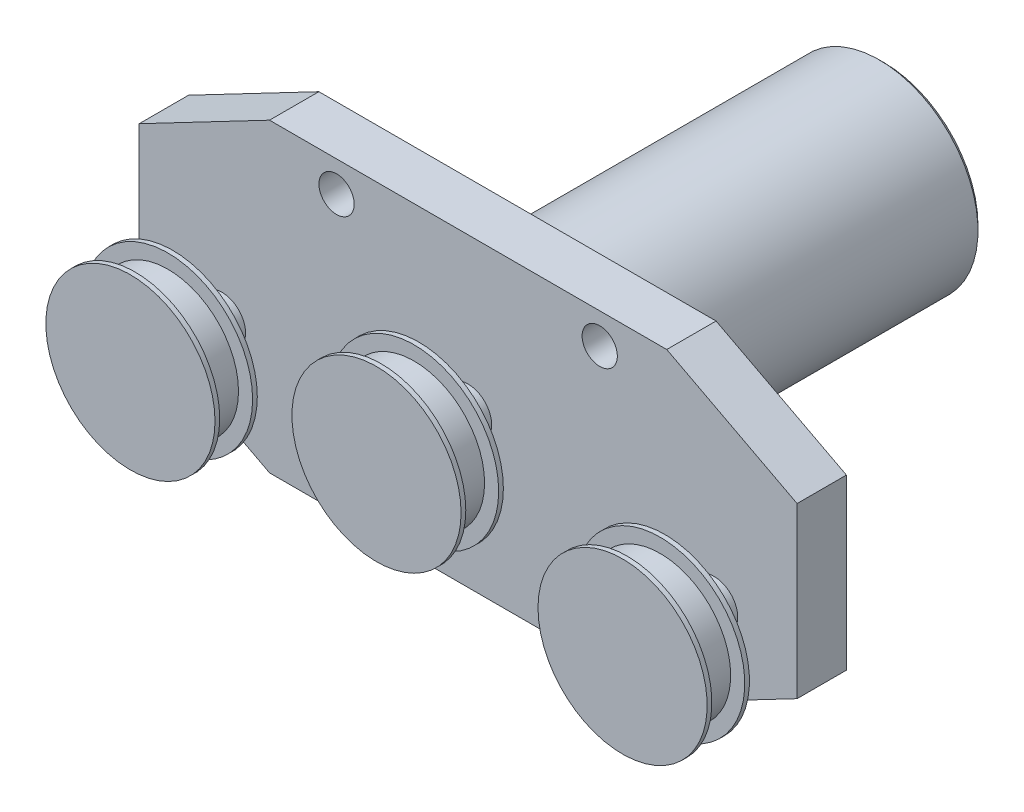
SolidWorks part; units mm, degrees
ref_plane "Front Plane" through (0, 0, 0) normal (0, 0, 1) x (1, 0, 0)
ref_plane "Top Plane" through (0, 0, 0) normal (0, 1, 0) x (1, 0, 0)
ref_plane "Right Plane" through (0, 0, 0) normal (1, 0, 0) x (0, 0, -1)
sketch "Sketch1" plane through (0, 0, 0) normal (0, 0, 1) x (1, 0, 0)
  line L0 (-21.1322, 32.5) -> (-48.8678, 17.9819)
  line L1 (-21.1322, 32.5) -> (21.1322, 32.5)
  line L2 (-21.1322, 32.5) -> (-21.1322, -32.5)
  line L3 (-21.1322, -32.5) -> (21.1322, -32.5)
  line L4 (21.1322, 32.5) -> (21.1322, -32.5)
  line L5 (-21.1322, 32.5) -> (21.1322, -32.5) construction
  line L6 (-21.1322, -32.5) -> (21.1322, 32.5) construction
  line L7 (-48.8678, 17.9819) -> (-21.1322, 17.9819)
  line L8 (-48.8678, 17.9819) -> (-48.8678, -17.9819)
  line L9 (-48.8678, -17.9819) -> (-21.1322, -17.9819)
  line L10 (-21.1322, 17.9819) -> (-21.1322, -17.9819)
  line L11 (-48.8678, 17.9819) -> (-21.1322, -17.9819) construction
  line L12 (-48.8678, -17.9819) -> (-21.1322, 17.9819) construction
  line L13 (-48.8678, -17.9819) -> (-21.1322, -32.5)
  line L14 (54.5227, 0) -> (-54.5227, 0) construction
  circle A0 centre (-6.8678, 26) radius 2.25
  circle A1 centre (-6.8678, -26) radius 2.25
  point P0 (0, 0)
  point P6 (-35, 0)
  point P13 (-45.9419, 15.6023)
  point P14 (-48.2557, -12.9347)
  point P19 (-48.8678, 17.9819)
  dimension "D5" = 4.5
  dimension "D1" = 70
  dimension "D2" = 65
  dimension "D3" = 28
  dimension "D4" = 26
extrude "Boss-Extrude1" add sketch "Sketch1" along normal blind 10.5 contours L9 L13 L2 | L8 L9 L2 L7 | L0 L7 L2 | L4 L1 L2 L3 A0 A1 region at (-30.3774, 22.8213, 0) region at (0.0805, 0, 0) region at (-35, 0, 0) region at (-30.3774, -22.8213, 0)
mirror "Mirror1" about plane through (21.1322, 0, 10.5) normal (1, 0, 0) of "Boss-Extrude1"
sketch "Sketch3" plane through (0, 0, 10.5) normal (0, 0, 1) x (1, 0, 0)
  line L0 (21.1322, 32.5) -> (21.1322, -32.5) construction
  line L1 (-21.1322, 32.5) -> (63.3965, 32.5) construction
  line L2 (-21.1322, -32.5) -> (63.3965, -32.5) construction
  circle A0 centre (21.1322, 0) radius 5
  circle A1 centre (-31.2329, -9.2764) radius 5
  circle A2 centre (73.4972, -9.2764) radius 5
  dimension "D1" = 10
extrude "Boss-Extrude2" add sketch "Sketch3" along normal blind 10.5
sketch "Sketch4" plane through (0, 0, 10.5) normal (0, 0, 1) x (1, 0, 0)
  line L0 (11.55, 0) -> (-11.55, 0) construction
  line L1 (21.1322, 32.5) -> (21.1322, -31.5094) construction
  line L2 (-21.1322, 32.5) -> (63.3965, 32.5) construction
  circle A0 centre (-6.8678, -26) radius 3.75
  circle A1 centre (-6.8678, 26) radius 3.75
  circle A2 centre (49.1322, 26) radius 3.75
  circle A3 centre (49.1322, -26) radius 3.75
  dimension "D1" = 7.5
extrude "Cut-Extrude1" cut sketch "Sketch4" against normal blind 6
sketch "Sketch5" plane through (0, 0, 21) normal (0, 0, 1) x (1, 0, 0)
  circle A0 centre (21.1322, 0) radius 18
  circle A1 centre (-31.2329, -9.2764) radius 18
  dimension "D1" = 36
extrude "Boss-Extrude3" add sketch "Sketch5" along normal blind 9
ref_plane "Plane1" through (0, 0, 29) normal (0, 0, 1) x (1, 0, 0)
sketch "Sketch7" plane through (0, 0, 29) normal (0, 0, 1) x (1, 0, 0)
  line L1 (-114.8475, 40.6416) -> (52.3817, 40.6416)
  line L2 (-114.8475, 40.6416) -> (-114.8475, -59.1944)
  line L3 (-114.8475, -59.1944) -> (52.3817, -59.1944)
  line L4 (52.3817, 40.6416) -> (52.3817, -59.1944)
  line L5 (-114.8475, 40.6416) -> (52.3817, -59.1944) construction
  line L6 (-114.8475, -59.1944) -> (52.3817, 40.6416) construction
  circle A0 centre (-31.2329, -9.2764) radius 15
  circle A1 centre (21.1322, 0) radius 15
  dimension "D1" = 30
extrude "Cut-Extrude2" cut sketch "Sketch7" against normal blind 7
ref_plane "Plane2" through (21.1322, 0, 0) normal (1, 0, 0) x (0, 0, -1)
mirror "Mirror2" about plane through (21.1322, 0, 0) normal (1, 0, 0) of bodies 106
sketch "Sketch8" plane through (0, 0, 0) normal (0, 0, -1) x (-1, 0, 0)
  circle A0 centre (-21.1322, 0) radius 21
  dimension "D1" = 42
extrude "Boss-Extrude4" add sketch "Sketch8" along normal blind 78
chamfer "Chamfer1" distance 1 angle 45 1 edges at (0.1322, 0, -78)
